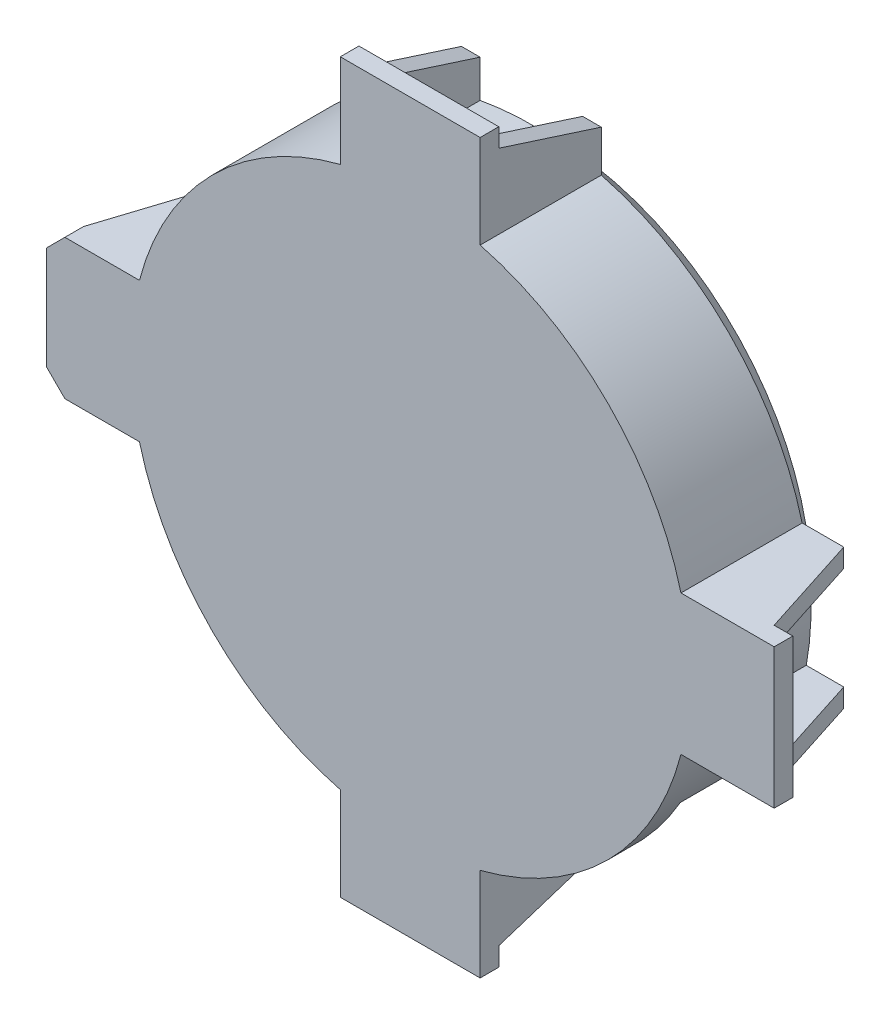
SolidWorks part; units mm, degrees
ref_plane "Plan de face" through (0, 0, 0) normal (0, 0, 1) x (1, 0, 0)
ref_plane "Plan de dessus" through (0, 0, 0) normal (0, 1, 0) x (1, 0, 0)
ref_plane "Plan de droite" through (0, 0, 0) normal (1, 0, 0) x (0, 0, -1)
sketch "Esquisse1" plane through (0, 0, 0) normal (0, 0, 1) x (1, 0, 0)
  circle A0 centre (0, 0) radius 150
  dimension "D1" = 300
extrude "Boss.-Extru.1" add sketch "Esquisse1" along normal blind 75
chamfer "Chanfrein1" distance 10 angle 45 1 edges at (150, 0, 0)
sketch "Esquisse2" plane through (0, 0, 75) normal (0, 0, 1) x (1, 0, 0)
  line L1 (-195.2369, -37.5) -> (-145.2369, -37.5)
  line L2 (-195.2369, -37.5) -> (-195.2369, 37.5)
  line L3 (-195.2369, 37.5) -> (-145.2369, 37.5)
  circle A0 centre (0, 0) radius 150 construction
  circle A1 centre (0, 0) radius 150
  point P0 (-150, 0)
  circle M5 centre (0, 0) radius 150
  dimension "D1" = 50
  dimension "D2" = 75
extrude "Boss.-Extru.2" add sketch "Esquisse2" against normal blind 10 contours L3 L2 L1 M5 region at (-171.8083, 0, 75)
chamfer "Chanfrein2" distance 10 angle 45 2 edges at (-195.2369, -37.5, 70) (-195.2369, 37.5, 70)
sketch "Esquisse3" plane through (0, 37.5, 0) normal (0, 1, 0) x (1, 0, 0)
  line L0 (-145.2369, -65) -> (-145.2369, -10)
  line L1 (150, -10) -> (-150, -10) construction
  line L2 (-145.2369, -10) -> (-167.5569, -10)
  line L3 (-167.5569, -10) -> (-185.2369, -65)
  line L4 (-185.2369, -65) -> (-145.2369, -65)
  line L5 (-185.2369, -65) -> (-185.2369, -75) construction
  line L6 (-185.2369, -65) -> (-145.2369, -65) construction
  dimension "D1" = 17.68
extrude "Boss.-Extru.3" add sketch "Esquisse3" against normal blind 10
sketch "Esquisse5" plane through (0, 0, 65) normal (0, 0, -1) x (-1, 0, 0)
  line L0 (185.2369, -37.5) -> (185.2369, 69.0879) construction
  line L2 (185.2369, 8.1134) -> (190.433, 11.1134)
  line L3 (190.433, 11.1134) -> (190.433, 17.1134)
  line L4 (190.433, 17.1134) -> (185.2369, 20.1134)
  line L5 (185.2369, 20.1134) -> (180.0407, 17.1134)
  line L6 (180.0407, 17.1134) -> (180.0407, 11.1134)
  line L7 (180.0407, 11.1134) -> (185.2369, 8.1134)
  circle A0 centre (185.2369, 14.1134) radius 5.1962 construction
  dimension "D1" = 6
extrude "Boss.-Extru.4" add sketch "Esquisse5" along normal blind 3.5
mirror "Symétrie1" about plane through (0, 0, 0) normal (0, 1, 0) of "Boss.-Extru.4", "Boss.-Extru.3"
pattern_circular "Répétition circulaire1" count 4 over 360 about axis through (0, 0, 75) along (0, 0, 1) of "Boss.-Extru.2", "Boss.-Extru.3", "Boss.-Extru.4", "Symétrie1"
sketch "Esquisse8" plane through (0, 0, 0) normal (0, 0, -1) x (-1, 0, 0)
  line L2 (-112.5833, -65) -> (-129.9038, -75)
  line L3 (-65, -112.5833) -> (-75, -129.9038)
  arc A0 (-145.2369, -37.5) -> (-37.5, -145.2369) centre (0, 0) ccw construction
  arc A1 (-129.9038, -75) -> (-75, -129.9038) centre (0, 0) ccw
  arc A2 (-112.5833, -65) -> (-65, -112.5833) centre (0, 0) ccw
extrude "Enlèv. mat.-Extru.3" cut sketch "Esquisse8" against normal blind 60
sketch "Esquisse9" plane through (0, 0, 0) normal (0, 0, -1) x (-1, 0, 0)
  circle A0 centre (0, 0) radius 110
  dimension "D1" = 220
extrude "Boss.-Extru.5" add sketch "Esquisse9" along normal blind 10
chamfer "Chanfrein3" distance 15 angle 45 1 edges at (-110, 0, -10)
sketch "Esquisse10" plane through (0, 0, -10) normal (0, 0, -1) x (-1, 0, 0)
  circle A0 centre (0, 0) radius 15
  dimension "D1" = 30
extrude "Boss.-Extru.6" add sketch "Esquisse10" along normal blind 20
